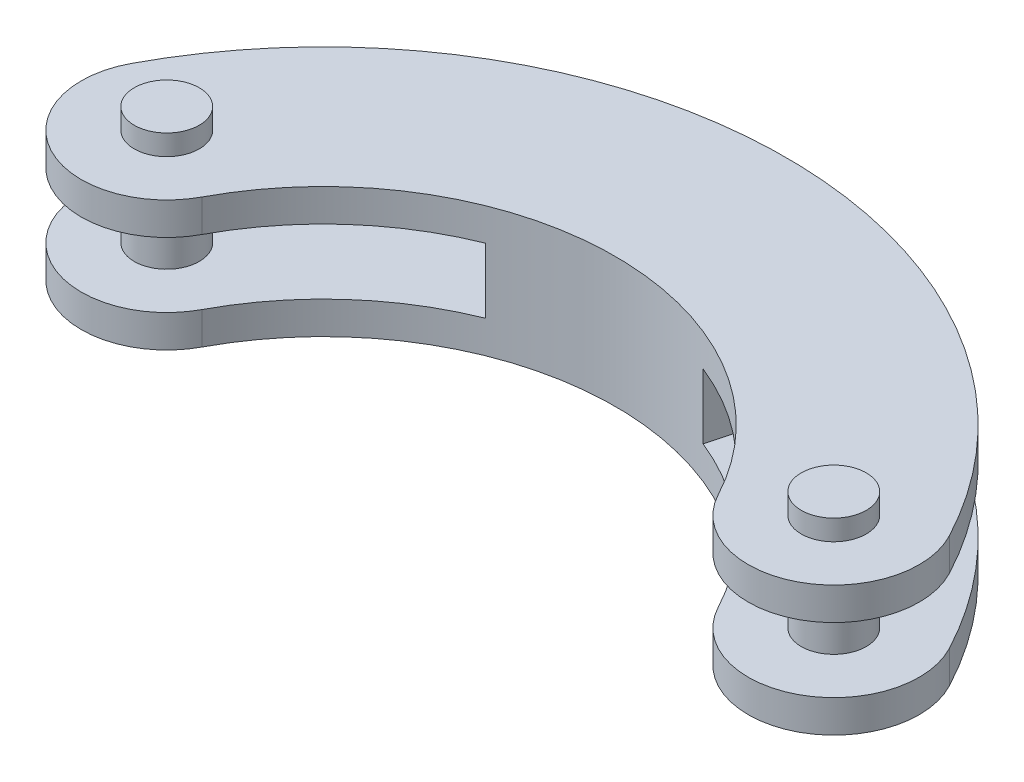
SolidWorks part; units mm, degrees
ref_plane "Front Plane" through (0, 0, 0) normal (0, 0, 1) x (1, 0, 0)
ref_plane "Top Plane" through (0, 0, 0) normal (0, 1, 0) x (1, 0, 0)
ref_plane "Right Plane" through (0, 0, 0) normal (1, 0, 0) x (0, 0, -1)
sketch "Sketch2" plane through (0, 0, 0) normal (0, 1, 0) x (1, 0, 0)
  line L0 (-97.5, -58.6208) -> (97.5, -58.6208) construction
  arc A0 (-97.5, -58.6208) -> (97.5, -58.6208) centre (0, -110.3929) cw construction
  arc A1 (119.5802, -46.8963) -> (-119.5802, -46.8963) centre (0, -110.3929) ccw
  arc A2 (75.4198, -70.3453) -> (-75.4198, -70.3453) centre (0, -110.3929) ccw
  arc A3 (75.4198, -70.3453) -> (119.5802, -46.8963) centre (97.5, -58.6208) ccw
  arc A4 (-119.5802, -46.8963) -> (-75.4198, -70.3453) centre (-97.5, -58.6208) ccw
  point P3 (0, 0)
  dimension "D2" = 25
  dimension "D1" = 195
extrude "Boss-Extrude1" add sketch "Sketch2" along normal blind 9.5
sketch "Sketch3" plane through (0, 9.5, 0) normal (0, 1, 0) x (1, 0, 0)
  line L0 (0, 67.1422) -> (0, 0) construction
  line L1 (0, 0) -> (0, -150) construction
  line L2 (0, -150) -> (-44.8435, 17.358)
  line L3 (0, -150) -> (44.8435, 17.358)
  arc A0 (119.5802, -46.8963) -> (-119.5802, -46.8963) centre (0, -110.3929) ccw construction
  arc M2 (119.5802, -46.8963) -> (-119.5802, -46.8963) centre (0, -110.3929) ccw
  arc M4 (-75.4198, -70.3453) -> (75.4198, -70.3453) centre (0, -110.3929) cw
  dimension "D1" = 150
  dimension "D2" = 15
extrude "Boss-Extrude2" add sketch "Sketch3" along normal blind 19 contours L3 L2 M4 M2 region at (0, 9.5, 0.9271)
sketch "Sketch4" plane through (0, 28.5, 0) normal (0, 1, 0) x (1, 0, 0)
  arc A0 (119.5802, -46.8963) -> (-119.5802, -46.8963) centre (0, -110.3929) ccw construction
  arc A1 (-119.5802, -46.8963) -> (-75.4198, -70.3453) centre (-97.5, -58.6208) ccw construction
  arc A2 (75.4198, -70.3453) -> (-75.4198, -70.3453) centre (0, -110.3929) ccw construction
  arc A3 (75.4198, -70.3453) -> (119.5802, -46.8963) centre (97.5, -58.6208) ccw construction
  arc A4 (119.5802, -46.8963) -> (-119.5802, -46.8963) centre (0, -110.3929) ccw
  arc A5 (-119.5802, -46.8963) -> (-75.4198, -70.3453) centre (-97.5, -58.6208) ccw
  arc A6 (75.4198, -70.3453) -> (-75.4198, -70.3453) centre (0, -110.3929) ccw
  arc A7 (75.4198, -70.3453) -> (119.5802, -46.8963) centre (97.5, -58.6208) ccw
extrude "Boss-Extrude3" add sketch "Sketch4" along normal blind 9.5
sketch "Sketch5" plane through (0, 38, 0) normal (0, 1, 0) x (1, 0, 0)
  circle A0 centre (-97.5, -58.6208) radius 9.5
  circle A1 centre (97.5, -58.6208) radius 9.5
  dimension "D1" = 19
  dimension "D2" = 19
extrude "Cut-Extrude1" cut sketch "Sketch5" against normal through all
extrude "Boss-Extrude4" add sketch "Sketch5<2>" against normal blind 50 from offset 6
sketch "Sketch5<2>" plane through (0, 38, 0) normal (0, 1, 0) x (1, 0, 0) same geometry as "Sketch5"
